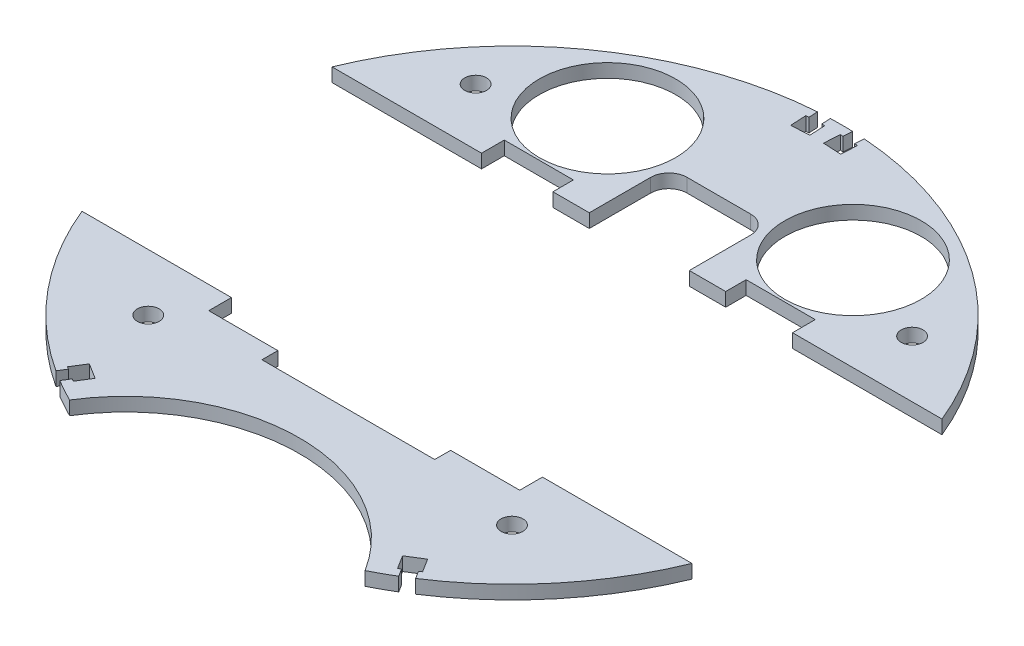
SolidWorks part; units mm, degrees
material "ABS"
ref_plane "Front Plane" through (0, 0, 0) normal (0, 0, 1) x (1, 0, 0)
ref_plane "Top Plane" through (0, 0, 0) normal (0, 1, 0) x (1, 0, 0)
ref_plane "Right Plane" through (0, 0, 0) normal (1, 0, 0) x (0, 0, -1)
sketch "Sketch1" plane through (0, 0, 0) normal (0, 1, 0) x (1, 0, 0)
  line L0 (0, -85) -> (-32.4891, -64.8129) construction
  line L1 (0, -85) -> (0, 0) construction
  arc A0 (32.4891, -64.8129) -> (-32.4891, -64.8129) centre (0, 0) ccw
  arc A1 (32.4891, -64.8129) -> (-32.4891, -64.8129) centre (0, -85) ccw
  dimension "D1" = 145
  dimension "D2" = 76.5
  dimension "D3" = 85
extrude "Boss-Extrude1" add sketch "Sketch1" along normal blind 3
sketch "solenoid placement" plane through (0, 3, 0) normal (0, 1, 0) x (1, 0, 0)
  line L4 (-19, -36) -> (19, -36)
  line L5 (-19, -36) -> (19, -36)
  line L6 (19, -36) -> (19, 28)
  line L7 (19, -36) -> (19, 28)
  line L8 (19, 28) -> (-19, 28)
  line L9 (19, 28) -> (-19, 28)
  line L10 (-19, 28) -> (-19, -36)
  line L11 (-19, 28) -> (-19, -36)
  circle A1 centre (0, 0) radius 72.5 construction
  arc A2 (32.4891, -64.8129) -> (-32.4891, -64.8129) centre (0, 0) ccw construction
  dimension "D1" = 0
extrude "Cut-Extrude1" cut sketch "solenoid placement" against normal through all
sketch "Sketch3" plane through (0, 3, 0) normal (0, 1, 0) x (1, 0, 0)
  circle A1 centre (27, 48) radius 12
  circle A2 centre (-27, 48) radius 12
  dimension "D1" = 24
extrude "Cut-Extrude3" cut sketch "Sketch3" against normal through all
sketch "Sketch4" plane through (0, 3, 0) normal (0, 1, 0) x (1, 0, 0)
  circle A2 centre (40, -40) radius 2.4
  circle A3 centre (40, -40) radius 2.4
  circle A4 centre (-40, -40) radius 2.4
  circle A5 centre (-40, -40) radius 2.4
  circle A6 centre (48, 40) radius 2.4
  circle A7 centre (48, 40) radius 2.4
  circle A8 centre (-48, 40) radius 2.4
  circle A12 centre (-48, 40) radius 2.4
  dimension "D1" = 0
  dimension "D2" = 0
  dimension "D3" = 0
  dimension "D4" = 0
extrude "Cut-Extrude4" cut sketch "Sketch4" against normal through all
sketch "Sketch2" plane through (0, 3, 0) normal (0, 1, 0) x (1, 0, 0)
  line L0 (0, 0) -> (0, 72.5) construction
  line L1 (34.2, -27.5) -> (34.2, -32.5)
  line L2 (67.082, -27.5) -> (34.2, -27.5)
  line L3 (34.2, 27.5) -> (67.082, 27.5)
  line L4 (34.2, 32.5) -> (34.2, 27.5)
  line L5 (22.2, 32.5) -> (34.2, 32.5)
  line L6 (19, 32.5) -> (22.2, 32.5)
  line L7 (19, -32.5) -> (19, 32.5)
  line L8 (22.2, -32.5) -> (19, -32.5)
  line L9 (-34.2, -32.5) -> (-22.2, -32.5)
  line L10 (-22.2, -32.5) -> (-19, -32.5)
  line L11 (-19, -32.5) -> (-19, 32.5)
  line L12 (-19, 32.5) -> (-22.2, 32.5)
  line L13 (-22.2, 32.5) -> (-34.2, 32.5)
  line L14 (-34.2, 32.5) -> (-34.2, 25)
  line L15 (-34.2, 25) -> (-68.0533, 25)
  line L16 (-68.0533, -25) -> (-34.2, -25)
  line L17 (-34.2, -25) -> (-34.2, -32.5)
  line L18 (-34.2, -32.5) -> (-22.2, -32.5)
  line L19 (-22.2, -32.5) -> (-19, -32.5)
  line L20 (-19, -32.5) -> (-19, 32.5)
  line L21 (-19, 32.5) -> (-22.2, 32.5)
  line L22 (-22.2, 32.5) -> (-34.2, 32.5)
  line L23 (-34.2, 32.5) -> (-34.2, 27.5)
  line L24 (-34.2, 27.5) -> (-67.082, 27.5)
  line L25 (-67.082, -27.5) -> (-34.2, -27.5)
  line L26 (-34.2, -27.5) -> (-34.2, -32.5)
  line L27 (34.2, -32.5) -> (22.2, -32.5)
  arc A0 (32.4891, -64.8129) -> (-32.4891, -64.8129) centre (0, 0) ccw construction
  arc A1 (67.082, 27.5) -> (67.082, -27.5) centre (0, 0) cw
  arc A2 (-68.0533, 25) -> (-68.0533, -25) centre (0, 0) ccw
  arc A3 (-67.082, 27.5) -> (-67.082, -27.5) centre (0, 0) ccw
  dimension "D2" = 55
  dimension "D1" = 0
extrude "Cut-Extrude2" cut sketch "Sketch2" against normal through all
sketch "Sketch5" plane through (0, 3, 0) normal (0, 1, 0) x (1, 0, 0)
  line L8 (-11, 28) -> (11, 28)
  line L9 (11, 28) -> (11, 41.5)
  line L10 (7, 45.5) -> (-7, 45.5)
  line L11 (-11, 41.5) -> (-11, 28)
  line L12 (19, 28) -> (-19, 28) construction
  arc A4 (11, 41.5) -> (7, 45.5) centre (7, 41.5) ccw
  arc A5 (-7, 45.5) -> (-11, 41.5) centre (-7, 41.5) ccw
  point P10 (0, 28)
  point P13 (0, 28)
  line M18 (-19, 28) -> (19, 28)
  dimension "D3" = 4
  dimension "D1" = 22
  dimension "D2" = 17.5
extrude "Cut-Extrude5" cut sketch "Sketch5" against normal through all contours L10 A5 L11 L9 A4 M18 region at (0, 3, -36.6073)
sketch "Sketch6" plane through (0, 3, 0) normal (0, 1, 0) x (-1, 0, 0)
  circle A1 centre (-27, -48) radius 15
  circle A2 centre (-27, -48) radius 15
  circle A3 centre (27, -48) radius 15
  circle A4 centre (27, -48) radius 15
  dimension "D1" = 0
  dimension "D2" = 0
extrude "Cut-Extrude10" cut sketch "Sketch6" against normal through all
sketch "Sketch7" plane through (0, 3, 0) normal (0, 1, 0) x (1, 0, 0)
  line L8 (-5.0378, 70.3327) -> (-5.6869, 70.2987)
  line L9 (-5.6869, 70.2987) -> (-5.5038, 66.8035)
  line L10 (-5.5038, 66.8035) -> (-1.5092, 67.0129)
  line L11 (-1.5092, 67.0129) -> (-1.6924, 70.5081)
  line L12 (-1.6924, 70.5081) -> (-2.3415, 70.474)
  line L13 (-2.3415, 70.474) -> (-2.4462, 72.4713)
  line L14 (-2.4462, 72.4713) -> (-5.1425, 72.33)
  line L15 (-5.1425, 72.33) -> (-5.0378, 70.3327)
  line L16 (-5.0378, 70.3327) -> (-5.6869, 70.2987)
  line L17 (-5.6869, 70.2987) -> (-5.5038, 66.8035)
  line L18 (-5.5038, 66.8035) -> (-1.5092, 67.0129)
  line L19 (-1.5092, 67.0129) -> (-1.6924, 70.5081)
  line L20 (-1.6924, 70.5081) -> (-2.3415, 70.474)
  line L21 (-2.3415, 70.474) -> (-2.4462, 72.4713)
  line L22 (-2.4462, 72.4713) -> (-5.1425, 72.33)
  line L23 (-5.1425, 72.33) -> (-5.0378, 70.3327)
  line L24 (5.6869, 70.2987) -> (5.0378, 70.3327)
  line L25 (5.5038, 66.8035) -> (5.6869, 70.2987)
  line L26 (1.5092, 67.0129) -> (5.5038, 66.8035)
  line L27 (1.6924, 70.5081) -> (1.5092, 67.0129)
  line L28 (2.3415, 70.474) -> (1.6924, 70.5081)
  line L29 (2.4462, 72.4713) -> (2.3415, 70.474)
  line L30 (5.1425, 72.33) -> (2.4462, 72.4713)
  line L31 (5.0378, 70.3327) -> (5.1425, 72.33)
  line L32 (5.6869, 70.2987) -> (5.0378, 70.3327)
  line L33 (5.5038, 66.8035) -> (5.6869, 70.2987)
  line L34 (1.5092, 67.0129) -> (5.5038, 66.8035)
  line L35 (1.6924, 70.5081) -> (1.5092, 67.0129)
  line L36 (2.3415, 70.474) -> (1.6924, 70.5081)
  line L37 (2.4462, 72.4713) -> (2.3415, 70.474)
  line L38 (5.1425, 72.33) -> (2.4462, 72.4713)
  line L39 (5.0378, 70.3327) -> (5.1425, 72.33)
  line L40 (38.5042, -59.072) -> (39.0554, -58.7276)
  line L41 (39.564, -60.7681) -> (38.5042, -59.072)
  line L42 (37.2743, -62.1989) -> (39.564, -60.7681)
  line L43 (36.2144, -60.5028) -> (37.2743, -62.1989)
  line L44 (35.6632, -60.8472) -> (36.2144, -60.5028)
  line L45 (33.8085, -57.8791) -> (35.6632, -60.8472)
  line L46 (37.2007, -55.7594) -> (33.8085, -57.8791)
  line L47 (39.0554, -58.7276) -> (37.2007, -55.7594)
  line L48 (38.5042, -59.072) -> (39.0554, -58.7276)
  line L49 (39.564, -60.7681) -> (38.5042, -59.072)
  line L50 (37.2743, -62.1989) -> (39.564, -60.7681)
  line L51 (36.2144, -60.5028) -> (37.2743, -62.1989)
  line L52 (35.6632, -60.8472) -> (36.2144, -60.5028)
  line L53 (33.8085, -57.8791) -> (35.6632, -60.8472)
  line L54 (37.2007, -55.7594) -> (33.8085, -57.8791)
  line L55 (39.0554, -58.7276) -> (37.2007, -55.7594)
  line L56 (-39.0554, -58.7276) -> (-38.5042, -59.072)
  line L57 (-37.2007, -55.7594) -> (-39.0554, -58.7276)
  line L58 (-33.8085, -57.8791) -> (-37.2007, -55.7594)
  line L59 (-35.6632, -60.8472) -> (-33.8085, -57.8791)
  line L60 (-36.2144, -60.5028) -> (-35.6632, -60.8472)
  line L61 (-37.2743, -62.1989) -> (-36.2144, -60.5028)
  line L62 (-39.564, -60.7681) -> (-37.2743, -62.1989)
  line L63 (-38.5042, -59.072) -> (-39.564, -60.7681)
  line L64 (-39.0554, -58.7276) -> (-38.5042, -59.072)
  line L65 (-37.2007, -55.7594) -> (-39.0554, -58.7276)
  line L66 (-33.8085, -57.8791) -> (-37.2007, -55.7594)
  line L67 (-35.6632, -60.8472) -> (-33.8085, -57.8791)
  line L68 (-36.2144, -60.5028) -> (-35.6632, -60.8472)
  line L69 (-37.2743, -62.1989) -> (-36.2144, -60.5028)
  line L70 (-39.564, -60.7681) -> (-37.2743, -62.1989)
  line L71 (-38.5042, -59.072) -> (-39.564, -60.7681)
  dimension "D1" = 0
  dimension "D2" = 0
  dimension "D3" = 0
  dimension "D4" = 0
extrude "Cut-Extrude11" cut sketch "Sketch7" against normal through all
equation "\"smallPulleyTeeth\"= 30"
equation "\"largePulleyTeeth\"= 30"
equation "\"eighthThick\"= 3.0mm"
equation "\"sixteenthThick\" = 1.7mm"
equation "\"quarterThick\"=6.0mm"
equation "\"OD\" = 145mm"
equation "\"puckAngle\" = 60.5deg"
equation "\"D1@Sketch1\"=\"OD\""
equation "\"puckDiam\" = 76.5mm"
equation "\"D2@Sketch1\"=\"puckDiam\""
equation "\"D1@Boss-Extrude1\"=\"eighthThick\""
equation "\"axlePress\" = 5.9mm"
equation "\"press\" = 0.2mm"
equation "\"wheelClear\" = 0.3mm"
equation "\"10-32clear\" = 4.8mm"
equation "\"6-32clear\" = 3.3mm"
equation "\"8-32clear\" = 4.0mm"
equation "\"wheelHeight\" = 22mm"
equation "\"wheelWell\" = 65mm"
equation "\"puckDist\" = 85mm"
equation "\"scoopFillet\" = 5mm"
equation "\"4-40clear\" = 3.0mm"
equation "\"D3@Sketch1\"=\"puckDist\""
